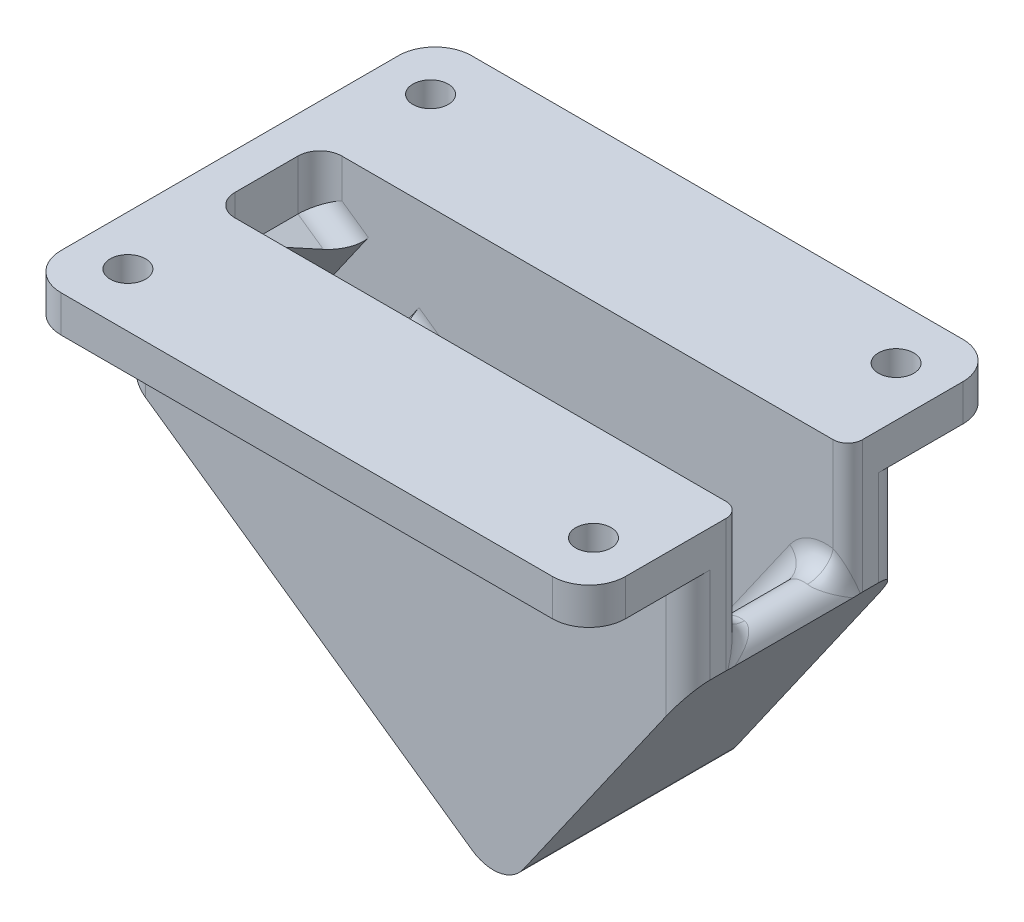
SolidWorks part; units mm, degrees
ref_plane "Front Plane" through (0, 0, 0) normal (0, 0, 1) x (1, 0, 0)
ref_plane "Top Plane" through (0, 0, 0) normal (0, 1, 0) x (1, 0, 0)
ref_plane "Right Plane" through (0, 0, 0) normal (1, 0, 0) x (0, 0, -1)
sketch "Sketch2" plane through (0, 0, 0) normal (0, 0, 1) x (1, 0, 0)
  line L0 (-38.5, 0) -> (38.5, 0)
  line L3 (-38.5, 0) -> (-38.5, -18)
  line L4 (-38.5, -18) -> (13.1678, -54.1782)
  line L5 (13.1678, -54.1782) -> (38.5, -18)
  line L6 (38.5, -18) -> (38.5, 0)
  line L7 (-23.3644, -13.9488) -> (-30.2473, -23.7786) construction
  line L8 (-33.5, -6.8517) -> (15.9549, -41.4805)
  line L9 (15.9549, -41.4805) -> (38.5, -9.2828)
  line L10 (9.4017, -36.8918) -> (2.5188, -46.7217) construction
  line L11 (-33.5, -6.8517) -> (-33.5, 0)
  point P10 (8.8091, -38.36)
  dimension "D1" = 35
  dimension "D2" = 18
  dimension "D3" = 12
  dimension "D4" = 77
  dimension "D5" = 5
  dimension "D6" = 40
  dimension "D7" = 5
  dimension "D8" = 8
extrude "Boss-Extrude1" add sketch "Sketch2" along normal mid plane 29 contours L8 L11 L0 L3 L4 L5 L6 L9 | L11 L8 L9 L6 L0 region at (-4.6234, -28.8629, 0) region at (6.1052, -14.229, 0)
extrude "Cut-Extrude1" cut sketch "Sketch2<4>" against normal mid plane 14.6 contours L11 L8 L9 L6 L0 region at (6.1052, -14.229, 0)
sketch "Sketch2<4>" plane through (0, 0, 0) normal (0, 0, 1) x (1, 0, 0) same geometry as "Sketch2"
sketch "Sketch3" plane through (0, 0, 0) normal (0, 1, 0) x (1, 0, 0)
  line L0 (38.5, -14.5) -> (38.5, -7.3) construction
  line L1 (-38.5, 28) -> (38.5, 28)
  line L2 (-38.5, 28) -> (-38.5, -28)
  line L3 (-38.5, -28) -> (38.5, -28)
  line L4 (38.5, 28) -> (38.5, -28)
  line L5 (-38.5, -14.5) -> (-38.5, 14.5) construction
  line L6 (-31.75, 20.6375) -> (31.75, -20.6375) construction
  line L7 (-31.75, 20.6375) -> (31.75, 20.6375) construction
  line L8 (-31.75, 20.6375) -> (-31.75, -20.6375) construction
  line L9 (-31.75, -20.6375) -> (31.75, -20.6375) construction
  line L10 (31.75, 20.6375) -> (31.75, -20.6375) construction
  line L11 (-38.5, 14.5) -> (38.5, 14.5) construction
  line L12 (-38.5, 14.5) -> (38.5, 14.5)
  line L13 (-38.5, -14.5) -> (38.5, -14.5) construction
  line L14 (-38.5, -14.5) -> (38.5, -14.5)
  circle A0 centre (-31.75, 20.6375) radius 2.413
  circle A1 centre (-31.75, -20.6375) radius 2.413
  circle A2 centre (31.75, 20.6375) radius 2.413
  circle A3 centre (31.75, -20.6375) radius 2.413
  point P9 (-38.5, 0)
  point P18 (31.75, 20.6375)
  point P19 (31.75, -20.6375)
  line M8 (38.5, 14.5) -> (-38.5, 14.5)
  line M10 (-38.5, -14.5) -> (38.5, -14.5)
  dimension "D2" = 4.826
  dimension "D1" = 56
  dimension "D3" = 41.275
  dimension "D4" = 63.5
extrude "Boss-Extrude2" add sketch "Sketch3" against normal blind 5 contours L4 L1 L2 A2 A0 M8 | L4 L2 L3 A3 A1 M10 region at (0, 0, -21.2723) region at (0, 0, 21.2723)
sketch "Sketch4" plane through (-14.2404, -20.3374, 0) normal (0.5736, 0.8192, 0) x (0.8192, -0.5736, 0)
  line L0 (-13.3249, 0) -> (26.6751, 0) construction
  line L1 (-23.5116, 7.3) -> (36.8617, -7.3) construction
  line L3 (-9.1103, -7.3) -> (-4.8956, 0)
  line L4 (-4.8956, 0) -> (-9.1103, 7.3)
  line L5 (-9.1103, 7.3) -> (-17.5396, 7.3)
  line L6 (-17.5396, 7.3) -> (-21.7542, 0)
  line L7 (-21.7542, 0) -> (-17.5396, -7.3)
  line L8 (-17.5396, -7.3) -> (-9.1103, -7.3)
  line L9 (35.1044, 0) -> (30.8897, 7.3)
  line L10 (30.8897, 7.3) -> (22.4604, 7.3)
  line L11 (22.4604, 7.3) -> (18.2458, 0)
  line L12 (18.2458, 0) -> (22.4604, -7.3)
  line L13 (22.4604, -7.3) -> (30.8897, -7.3)
  line L14 (30.8897, -7.3) -> (35.1044, 0)
  circle A0 centre (-13.3249, 0) radius 4.9
  circle A1 centre (26.6751, 0) radius 4.9
  circle A2 centre (-13.3249, 0) radius 7.3 construction
  circle A3 centre (26.6751, 0) radius 7.3 construction
  point P9 (6.6751, 0)
  dimension "D2" = 9.8
  dimension "D1" = 40
  dimension "D3" = 14.6
extrude "Cut-Extrude2" cut sketch "Sketch4" against normal blind 6.35
extrude "Cut-Extrude3" cut sketch "Sketch4<2>" against normal through all contours A0 | A1
sketch "Sketch4<2>" plane through (-14.2404, -20.3374, 0) normal (0.5736, 0.8192, 0) x (0.8192, -0.5736, 0) same geometry as "Sketch4"
fillet "Fillet1" radius 3 2 edges at (38.5, -9.2828, 0) (15.9549, -41.4805, 0)
fillet "Fillet2" radius 5 4 edges at (-38.5, -2.5, 28) (-38.5, -2.5, -28) (38.5, -2.5, -28) (38.5, -2.5, 28)
fillet "Fillet3" radius 5 1 edges at (13.1678, -54.1782, 0)
fillet "Fillet5" radius 2 2 edges at (38.5, -9, -7.3) (38.5, -9, 7.3)
fillet "Fillet6" radius 3 16 edges at (12.2802, -38.9074, 7.3) (15.7392, -40.2567, 7.3) (37.7403, -16.8022, 7.731) (34.5847, -15.9406, 7.3) (37.3528, -16.4381, -7.4909) (34.5847, -15.9406, -7.3) (25.3591, -28.0499, -7.3) (15.7392, -40.2567, -7.3) (-33.5, -3.4259, 7.3) (-33.5, -3.4259, -7.3) (-31.054, -8.5644, -7.3) (-31.054, -8.5644, 7.3) (-8.7725, -24.1661, 7.3) (25.3591, -28.0499, 7.3) (-8.7725, -24.1661, -7.3) (12.2802, -38.9074, -7.3)
fillet "Fillet7" radius 3 4 edges at (38.5, -11.5, 14.5) (38.5, -11.5, -14.5) (-38.5, -11.5, 14.5) (-38.5, -11.5, -14.5)
